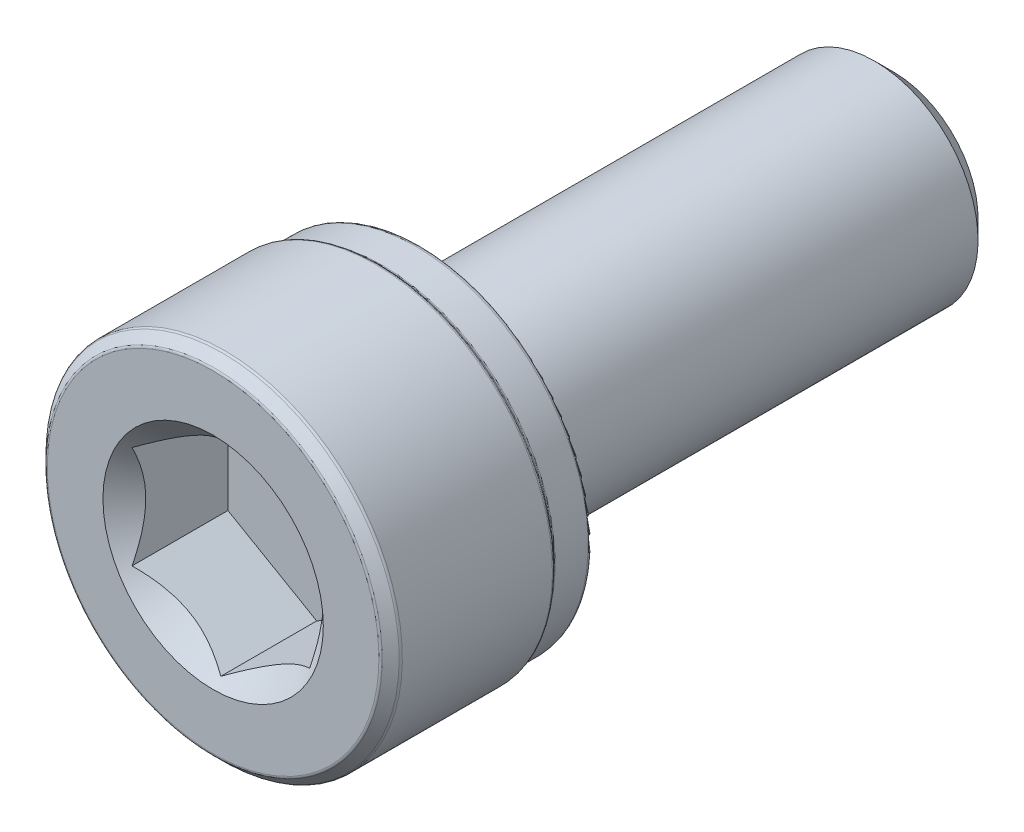
SolidWorks part; units mm, degrees
ref_plane "Front Plane" through (0, 0, 0) normal (0, 0, 1) x (1, 0, 0)
ref_plane "Top Plane" through (0, 0, 0) normal (0, 1, 0) x (1, 0, 0)
ref_plane "Right Plane" through (0, 0, 0) normal (1, 0, 0) x (0, 0, -1)
sketch "Sketch1" plane through (0, 0, 0) normal (1, 0, 0) x (0, 0, -1)
  line L0 (-11.5, 0) -> (11.5, 0) construction
  line L1 (11.5, 0) -> (11.5, 2.8505) construction
  line L2 (11.5, 2.8505) -> (10.8505, 3.5) construction
  line L3 (10.8505, 3.5) -> (10.75, 3.5) construction
  line L4 (10.75, 3.5) -> (-4.5, 3.5) construction
  line L5 (-4.5, 3.5) -> (-4.5, 6) construction
  line L6 (-4.5, 6) -> (-11.5, 6) construction
  line L7 (-11.5, 6) -> (-11.5, 0) construction
  line L8 (11.5, 2.8505) -> (11.5, 3.5) construction
  line L9 (11.4375, 3.6083) -> (11.9375, 2.7422) construction
  line L10 (11.9375, 2.7422) -> (12.4375, 3.6083) construction
  line L11 (12.4375, 3.6083) -> (11.4375, 3.6083) construction
  line L12 (11.9375, 3.6083) -> (11.9375, 3.5) construction
  line L13 (11.9375, 2.7422) -> (11.9375, 2.8505) construction
  line L14 (11.875, 2.8505) -> (12, 2.8505) construction
  line L15 (11.5, 3.5) -> (12.375, 3.5) construction
  line L16 (11.4688, 3.5541) -> (12.4062, 3.5541) construction
  line L17 (11.5, 0) -> (11.5, -3.5) construction
  line L18 (-4.85, 6) -> (-4.5, 5.65) construction
  line L19 (-11.15, 6) -> (-11.5, 5.65) construction
  line L20 (-4.5, 3.5) -> (-4.5, 0) construction
  line L21 (-4.5, 1.75) -> (0.8333, 1.75) construction
  line L22 (0.8333, 1.75) -> (6.1667, 1.75) construction
  line L23 (6.1667, 1.75) -> (11.5, 1.75) construction
  line L24 (0.8333, 1.75) -> (0.8333, 3.5) construction
  line L25 (0.8333, 3.5) -> (0.8333, 6) construction
  line L26 (6.1667, 1.75) -> (6.1667, 6) construction
  point P0 (-11.5, 3)
  point P3 (9, 3.5)
  point P4 (0, 0)
  point P18 (6.1667, 3.5)
  point P22 (11.9375, 2.8505)
  point P24 (10.75, 3.5)
  point P25 (11.9375, 3.5)
  point P28 (11.9375, 3.5541)
  point P29 (9, -3.5)
  point P30 (0.8333, 3.5)
  point P31 (-8, 6)
  point P37 (-5.725, 6)
  point P38 (-10.975, 6)
  point P45 (0.8333, 1.75)
  point P46 (6.1667, 1.75)
  dimension "D1" = 45
  dimension "D2" = 0.125
  dimension "D7" = 0.35
  dimension "D8" = 0.35
  dimension "D9" = 0.35
  dimension "D10" = 0.175
  dimension "D11" = 0.875
  dimension "Drive Size" = 6
  dimension "Head Diameter" = 12
  dimension "Head Height" = 7
  dimension "Thread Pitch" = 1
  dimension "Thread Dia" = 7
  dimension "Length" = 16
  dimension "D12" = 0.75
  dimension "D4" = 2.5
  dimension "Key Engagement" = 3.5
sketch "Sketch2" plane through (0, 0, 0) normal (1, 0, 0) x (0, 0, -1)
  line L0 (-11.5, 0) -> (-11.5, 5.6047)
  line L1 (-11.1047, 6) -> (-6.0328, 6)
  line L2 (-4.5, 5.675) -> (-4.5, 3.85)
  line L4 (10.8505, 3.5) -> (11.5, 2.8505)
  line L5 (11.5, 2.8505) -> (11.5, 0)
  line L6 (-4.5, 6) -> (-11.5, 6) construction
  line L7 (11.5, 0) -> (-11.5, 0)
  line L8 (-11.15, 6) -> (-11.5, 5.65) construction
  line L10 (-11.182, 5.968) -> (-11.468, 5.682)
  line L12 (-5.7672, 5.825) -> (-4.65, 5.825)
  line L14 (-4.85, 6) -> (-4.5, 5.65) construction
  line L15 (-5.9555, 5.968) -> (-5.8445, 5.857)
  line L17 (-4.5, 3.5) -> (-4.5, 6) construction
  line L19 (-4.15, 3.5) -> (10.8505, 3.5)
  line L20 (10.75, 3.5) -> (-4.5, 3.5) construction
  arc A0 (-4.65, 5.825) -> (-4.5, 5.675) centre (-4.65, 5.675) cw
  arc A1 (-4.5, 3.85) -> (-4.15, 3.5) centre (-4.15, 3.85) ccw
  arc A2 (-11.182, 5.968) -> (-11.1047, 6) centre (-11.1047, 5.8906) cw
  arc A3 (-11.468, 5.682) -> (-11.5, 5.6047) centre (-11.3906, 5.6047) ccw
  arc A4 (-5.9555, 5.968) -> (-6.0328, 6) centre (-6.0328, 5.8906) ccw
  arc A5 (-5.8445, 5.857) -> (-5.7672, 5.825) centre (-5.7672, 5.9344) ccw
  point P22 (-4.675, 5.825)
  point P37 (-5.8125, 5.825)
  dimension "D2" = 0.15
  dimension "D3" = 0.35
  dimension "D4" = 0.1094
  dimension "D1" = 1.3125
revolve "Revolve1" add sketch "Sketch2" angle 360 about L7
sketch "Sketch3" plane through (0, 0, 11.5) normal (0, 0, 1) x (1, 0, 0)
  line L1 (3, -1.7321) -> (3, 1.7321)
  line L2 (3, 1.7321) -> (0, 3.4641)
  line L3 (0, 3.4641) -> (-3, 1.7321)
  line L4 (-3, 1.7321) -> (-3, -1.7321)
  line L5 (-3, -1.7321) -> (0, -3.4641)
  line L6 (0, -3.4641) -> (3, -1.7321)
  circle A0 centre (0, 0) radius 3 construction
  circle A1 centre (0, 0) radius 6 construction
  circle A2 centre (0, 0) radius 6 construction
  circle A3 centre (0, 0) radius 3.4641 construction
  dimension "D1" = 6.9282
extrude "Cut-Extrude1" cut sketch "Sketch3" against normal up to vertex (3.5 mm away) up to point (0, 6, 8)
sketch "Sketch4" plane through (0, 0, 11.5) normal (0, 0, 1) x (1, 0, 0)
  circle A0 centre (0, 0) radius 3.7239
  dimension "D1" = 7.4478
extrude "Cut-Extrude2" cut sketch "Sketch4" against normal up to vertex (3.5 mm away) draft 45 up to point (0, 6, 8)
sketch "Sketch6" [suppressed] plane through (0, 0, -11.5) normal (0, 0, -1) x (-1, 0, 0)
  circle A0 centre (0, 0) radius 3.5
curve "Helix/Spiral1" [suppressed] pitch 1 height 17 turns 17
sketch "Sketch7" [suppressed] plane through (0, 0, 0) normal (1, 0, 0) x (0, 0, -1)
  line L0 (11.4688, 3.5541) -> (12.4062, 3.5541)
  line L1 (12.4062, 3.5541) -> (12, 2.8505)
  line L2 (12, 2.8505) -> (11.875, 2.8505)
  line L3 (11.875, 2.8505) -> (11.4688, 3.5541)
sweep "Cut-Sweep1" [suppressed] cut profiles "Sketch7" path "Helix/Spiral1"
sketch "Sketch8" [suppressed] plane through (0, 0, 0) normal (1, 0, 0) x (0, 0, -1)
  line L0 (-8, 0) -> (-8, 3.85)
  line L1 (-8, 1.7321) -> (-8, 3.4641) construction
  line L2 (-4.15, 3.5) -> (-4, 3.5)
  line L3 (-4.5, 3.85) -> (-8, 3.85)
  line L4 (-4, 3.5) -> (-1.9793, 0)
  line L5 (-1.9793, 0) -> (-8, 0)
  line L7 (-11.5, 0) -> (11.5, 0) construction
  line L8 (-4.5, 3.5) -> (-4.5, 6) construction
  arc A0 (-4.5, 3.85) -> (-4.15, 3.5) centre (-4.15, 3.85) ccw construction
  arc A1 (-4.5, 3.85) -> (-4.15, 3.5) centre (-4.15, 3.85) ccw
  dimension "D1" = 60
  dimension "D2" = 0.5
revolve "Revolve2" [suppressed] add sketch "Sketch8" angle 360 about L5
sketch "Sketch9" [suppressed] plane through (0, 0, 11.5) normal (0, 0, 1) x (1, 0, 0)
  line L0 (-0.0274, 5.8861) -> (-0.15, 6.1599)
  line L1 (-0.15, 6.1599) -> (0.15, 6.1599)
  line L2 (0.15, 6.1599) -> (0.0274, 5.8861)
  line L3 (0, 6) -> (0, 5.65) construction
  line L4 (0, 0) -> (-0.15, 6.1599) construction
  line L5 (0.15, 6.1599) -> (0, 0) construction
  circle A0 centre (0, 0) radius 5.825 construction
  arc A4 (-0.0274, 5.8861) -> (0.0274, 5.8861) centre (0, 5.8984) ccw
  point P10 (0, 5.825)
  point P19 (0, 5.825)
  dimension "D2" = 0.03
  dimension "D1" = 0.3
  dimension "D3" = 2.79
extrude "Cut-Extrude3" [suppressed] cut sketch "Sketch9" against normal through all
pattern_circular "CirPattern1" [suppressed] count 80 over 360 of bodies 112
equation "\"D2@Sketch1\" = \"Thread Pitch@Sketch1\" / 8"
equation "\"D4@Helix/Spiral1\" = \"Thread Pitch@Sketch1\""
equation "\"D7@Sketch1\" = \"Head Height@Sketch1\" * .05"
equation "\"D8@Sketch1\"=\"D7@Sketch1\""
equation "\"D9@Sketch1\"=\"D7@Sketch1\""
equation "\"D10@Sketch1\"=\"D7@Sketch1\"/2"
equation "\"D11@Sketch1\"=\"D10@Sketch1\"*5"
equation "\"D4@Sketch1\"=\"Thread Pitch@Sketch1\"*2.5"
equation "\"D12@Sketch1\"=\"Thread Pitch@Sketch1\"*.75"
equation "\"D3@Helix/Spiral1\"=\"Length@Sketch1\"+\"Thread Pitch@Sketch1\""
equation "\"D1@Sketch2\"=\"Head Height@Sketch1\"*0.1875"
equation "\"D2@Sketch2\"=\"Head Diameter@Sketch1\"*0.0125"
equation "\"D3@Sketch2\"=\"Thread Dia@Sketch1\"*0.05"
equation "\"D1@Sketch9\"=\"Head Diameter@Sketch1\"*0.025"
equation "\"D2@Sketch9\"=\"D1@Sketch9\"*0.1"
equation "\"D2@Sketch8\"=\"Thread Pitch@Sketch1\"*00.5"
equation "\"D4@Sketch2\"=\"D8@Sketch1\"*0.3125"
equation "\"D1@CirPattern1\"=int ((360/\"D3@Sketch9\")*0.625)"
equation "\"D1@Sketch4\"=\"D1@Sketch3\" * 01.075"
